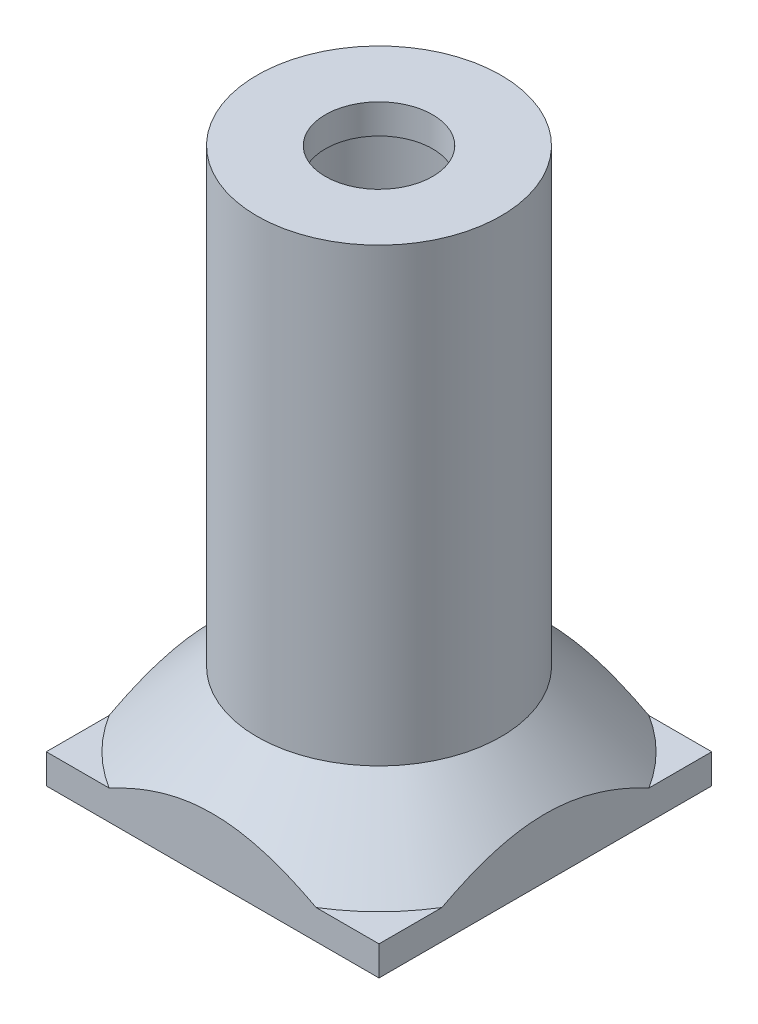
SolidWorks part; units mm, degrees
ref_plane "Front Plane" through (0, 0, 0) normal (0, 0, 1) x (1, 0, 0)
ref_plane "Top Plane" through (0, 0, 0) normal (0, 1, 0) x (1, 0, 0)
ref_plane "Right Plane" through (0, 0, 0) normal (1, 0, 0) x (0, 0, -1)
sketch "Sketch2" plane through (0, 0, 0) normal (0, 1, 0) x (1, 0, 0)
  line L1 (-22.4535, 22.5) -> (22.5465, 22.5)
  line L2 (-22.4535, 22.5) -> (-22.4535, -22.5)
  line L3 (-22.4535, -22.5) -> (22.5465, -22.5)
  line L4 (22.5465, 22.5) -> (22.5465, -22.5)
  circle A0 centre (0, 0) radius 7.25
  circle A1 centre (0, 0) radius 12.5
  circle A2 centre (0, 0) radius 16.5
  dimension "D1" = 14.5
  dimension "D2" = 25
  dimension "D3" = 33
  dimension "D4" = 45
  dimension "D5" = 22.4535
  dimension "D6" = 22.5
extrude "Boss-Extrude1" add sketch "Sketch2" along normal blind 4 contours A2 A1 | A1 A0 region at (-12.1464, 0, 0) region at (-16.0333, 0, 0)
extrude "Boss-Extrude3" add sketch "Sketch2<4>" against normal blind 67 contours A2 A1 region at (-16.0333, 0, 0)
sketch "Sketch2<4>" plane through (0, 0, 0) normal (0, 1, 0) x (1, 0, 0) same geometry as "Sketch2"
sketch3d "3DSketch1"
  circle A0 centre (0, -67, 0) radius 16.5 construction
  point P0 (-1.1452, -67, 16.4602)
  point P3 (0, -50.5, 0)
ref_plane "Plane2" through (0, -67, 0) normal (0, -1, 0) x (-1, 0, 0)
sketch "Sketch3" plane through (0, -67, 0) normal (0, -1, 0) x (-1, 0, 0)
  line L1 (-22.5, 22.5) -> (22.5, 22.5)
  line L2 (-22.5, 22.5) -> (-22.5, -22.5)
  line L3 (-22.5, -22.5) -> (22.5, -22.5)
  line L4 (22.5, 22.5) -> (22.5, -22.5)
  dimension "D1" = 45
  dimension "D2" = 22.5
  dimension "D3" = 22.5
extrude "Boss-Extrude4" add sketch "Sketch3" along normal blind 4
chamfer "Chamfer1" distance 10 angle 45 1 edges at (0, -67, 16.5)
